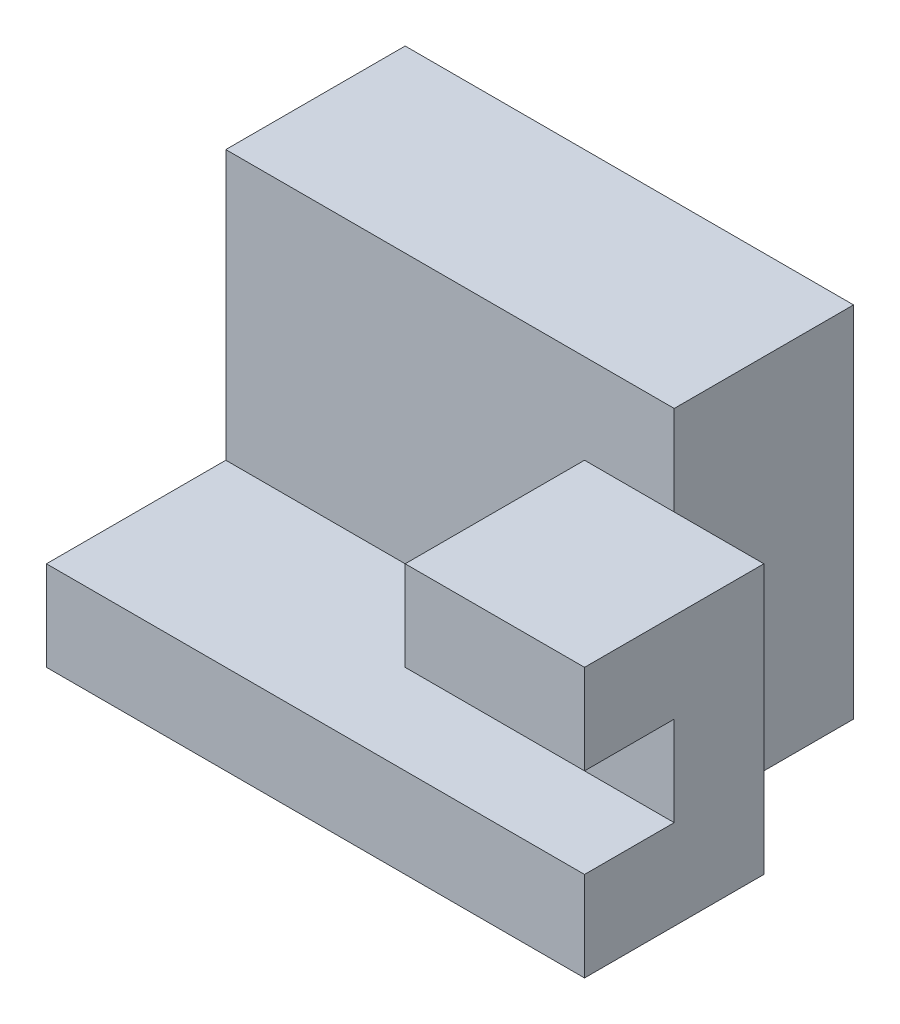
SolidWorks part; units mm, degrees
ref_plane "前基準面" through (0, 0, 0) normal (0, 0, 1) x (1, 0, 0)
ref_plane "上基準面" through (0, 0, 0) normal (0, 1, 0) x (1, 0, 0)
ref_plane "右基準面" through (0, 0, 0) normal (1, 0, 0) x (0, 0, -1)
sketch "草圖1" plane through (0, 0, 0) normal (0, 1, 0) x (1, 0, 0)
  line L0 (0, 0) -> (0, 10)
  line L1 (0, 10) -> (25, 10)
  line L2 (25, 10) -> (25, 0)
  line L3 (25, 0) -> (0, 0)
  line L4 (0, 0) -> (0, -10)
  line L5 (0, -10) -> (30, -10)
  line L6 (30, -10) -> (30, 0)
  line L7 (30, 0) -> (25, 0)
  dimension "D1" = 25
  dimension "D2" = 10
  dimension "D3" = 10
  dimension "D4" = 30
extrude "填料-伸長1" add sketch "草圖1" along normal blind 20 contours L3 L2 L1 L0 region at (12.5, 0, -5)
extrude "填料-伸長2" add sketch "草圖1<3>" along normal blind 5 contours L6 L7 L3 L4 L5 region at (15, 0, 5)
sketch "草圖1<3>" plane through (0, 0, 0) normal (0, 1, 0) x (1, 0, 0) same geometry as "草圖1"
sketch "草圖2" plane through (30, 0, 0) normal (1, 0, 0) x (0, 0, -1)
  line L0 (0, 5) -> (0, 11.3509)
  line L1 (0, 20) -> (0, 5) construction
  line L2 (-5, 10) -> (-10, 10)
  line L3 (-10, 10) -> (-10, 15)
  line L4 (-10, 15) -> (0, 15)
  line L5 (-5, 10) -> (-5, 5)
  line L6 (-10, 5) -> (0, 5) construction
  line L7 (-5, 5) -> (-10, 5)
  line L8 (-10, 5) -> (-10, 0)
  line L9 (-10, 0) -> (0, 0)
  line L10 (10, 20) -> (0, 20) construction
  line L11 (-5, 5) -> (-10, 5)
  line L12 (-10, 0) -> (0, 0)
  line L13 (0, 15) -> (0, 0)
  line M7 (0, 5) -> (-10, 5)
  dimension "D1" = 5
  dimension "D2" = 10
  dimension "D3" = 5
  dimension "D4" = 5
extrude "填料-伸長3" add sketch "草圖2" against normal blind 10 contours L13 L4 L3 L2 L5 L0 M7 region at (30, 10.8333, 4.1667)
